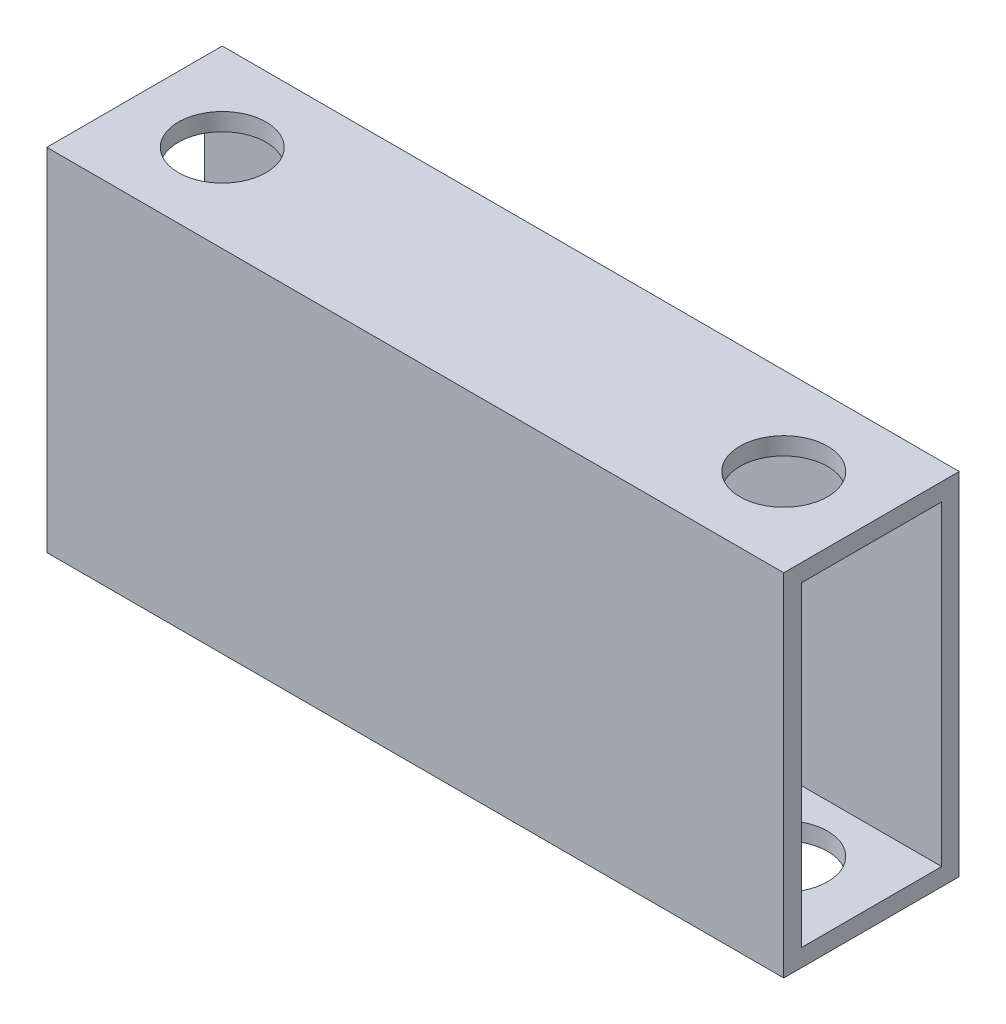
SolidWorks part; units mm, degrees
ref_plane "Front Plane" through (0, 0, 0) normal (0, 0, 1) x (1, 0, 0)
ref_plane "Top Plane" through (0, 0, 0) normal (0, 1, 0) x (1, 0, 0)
ref_plane "Right Plane" through (0, 0, 0) normal (1, 0, 0) x (0, 0, -1)
sketch "Sketch1" plane through (0, 0, 0) normal (1, 0, 0) x (0, 0, -1)
  line L0 (-4, -9) -> (-4, 9)
  line L1 (-5, -10) -> (5, -10)
  line L2 (-5, -10) -> (-5, 10)
  line L3 (-5, 10) -> (5, 10)
  line L4 (5, -10) -> (5, 10)
  line L5 (-5, -10) -> (5, 10) construction
  line L6 (-5, 10) -> (5, -10) construction
  line L7 (-4, 9) -> (4, 9)
  line L8 (4, -9) -> (4, 9)
  line L9 (-4, -9) -> (4, -9)
  point P0 (0, 0)
  dimension "D1" = 10
  dimension "D2" = 20
  dimension "D3" = 1
extrude "Boss-Extrude1" add sketch "Sketch1" along normal blind 21 and the other way blind 21
sketch "Sketch2" plane through (0, 10, 0) normal (0, 1, 0) x (1, 0, 0)
  line L1 (-21, 5) -> (-21, -5) construction
  line L2 (21, 5) -> (21, -5) construction
  circle A0 centre (-16, 0) radius 2.5
  circle A1 centre (16, 0) radius 2.5
  dimension "D4" = 5
  dimension "D5" = 5
  dimension "D3" = 5
  dimension "D6" = 5
extrude "Cut-Extrude1" cut sketch "Sketch2" against normal blind 20
